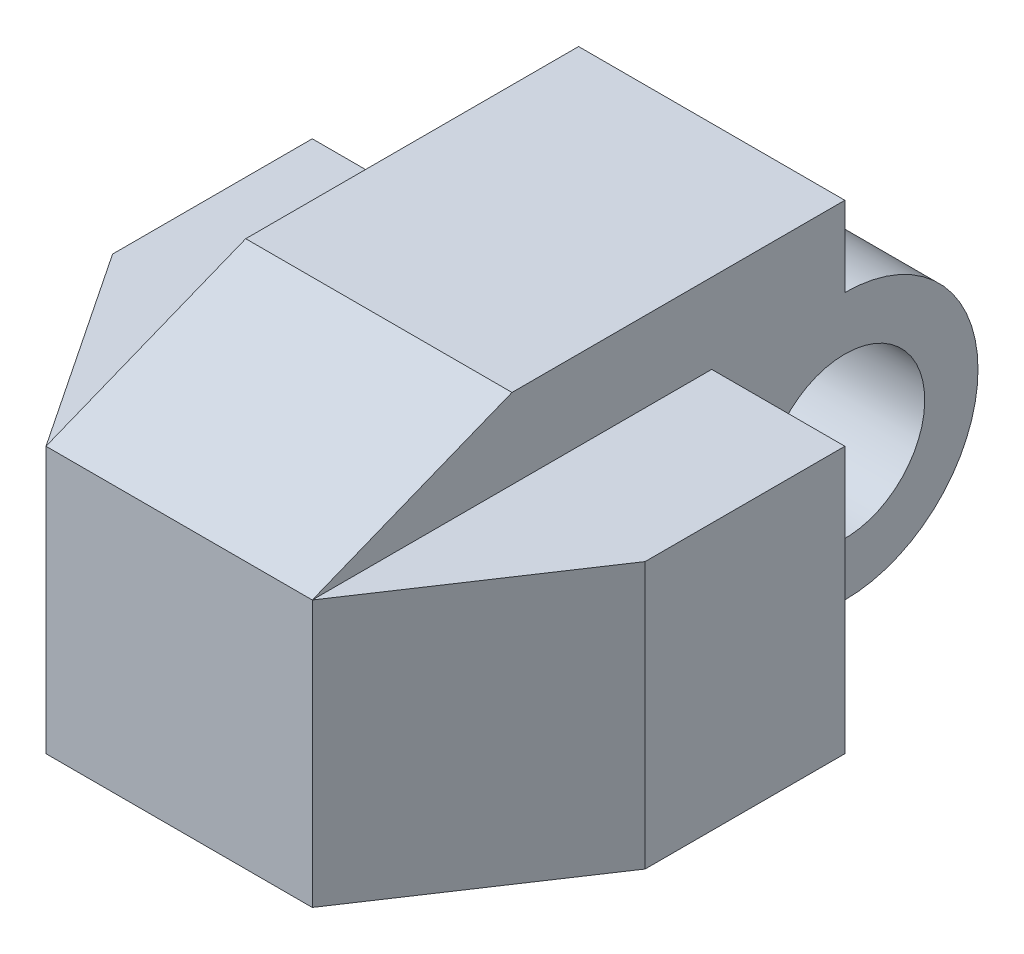
SolidWorks part; units mm, degrees
ref_plane "Front Plane" through (0, 0, 0) normal (0, 0, 1) x (1, 0, 0)
ref_plane "Top Plane" through (0, 0, 0) normal (0, 1, 0) x (1, 0, 0)
ref_plane "Right Plane" through (0, 0, 0) normal (1, 0, 0) x (0, 0, -1)
sketch "Sketch1" plane through (0, 0, 0) normal (0, 0, 1) x (1, 0, 0)
  line L2 (-3.6788, 4.8964) -> (6.3212, 4.8964)
  line L3 (-3.6788, 4.8964) -> (-3.6788, -5.1036)
  line L4 (-3.6788, -5.1036) -> (6.3212, -5.1036)
  line L5 (6.3212, 4.8964) -> (6.3212, -5.1036)
  dimension "D1" = 10
  dimension "D2" = 10
extrude "Boss-Extrude1" add sketch "Sketch1" along normal blind 10
sketch "Sketch2" plane through (6.3212, 0, 0) normal (1, 0, 0) x (0, 0, -1)
  circle A0 centre (-5, -0.1036) radius 3
extrude "Cut-Extrude1" cut sketch "Sketch2" against normal blind 10
fillet "Fillet2" radius 5 2 edges at (1.3212, -5.1036, 0) (1.3212, 4.8964, 0)
sketch "Sketch3" plane through (0, 0, 10) normal (0, 0, 1) x (1, 0, 0)
  line L0 (6.3212, 4.8964) -> (-3.6788, 4.8964) construction
  line L1 (-8.6788, 4.8964) -> (11.3212, 4.8964)
  line L2 (-8.6788, 4.8964) -> (-8.6788, -5.1036)
  line L3 (-8.6788, -5.1036) -> (11.3212, -5.1036)
  line L4 (11.3212, 4.8964) -> (11.3212, -5.1036)
  line L5 (-3.6788, 4.8964) -> (-3.6788, -5.1036) construction
  dimension "D1" = 0
  dimension "D2" = 10
  dimension "D3" = 20
  dimension "D4" = 5
extrude "Boss-Extrude3" add sketch "Sketch3" along normal blind 15
sketch "Sketch4" plane through (0, 4.8964, 0) normal (0, 1, 0) x (1, 0, 0)
  line L0 (-8.6788, -25) -> (-8.6788, -10) construction
  line L13 (6.3212, -25) -> (11.3212, -17.5)
  line L14 (11.3212, -25) -> (-8.6788, -25) construction
  line L17 (-3.6788, -25) -> (-8.6788, -17.5)
  line L18 (11.3212, -25) -> (11.3212, -17.5)
extrude "Cut-Extrude2" cut sketch "Sketch4" against normal blind 15
sketch "Sketch5" plane through (0, 4.8964, 0) normal (0, 1, 0) x (1, 0, 0)
  line L1 (-3.6788, -5) -> (6.3212, -5)
  line L2 (-3.6788, -5) -> (-3.6788, -25)
  line L3 (-3.6788, -25) -> (6.3212, -25)
  line L4 (6.3212, -5) -> (6.3212, -25)
extrude "Boss-Extrude4" add sketch "Sketch5" along normal blind 3
sketch "Sketch6" plane through (-3.6788, 0, 0) normal (-1, 0, 0) x (0, 0, 1)
  line L1 (5, 7.8964) -> (25, 7.8964) construction
  line L2 (17.5, 7.8964) -> (25, 4.8964)
  line L3 (25, 4.8964) -> (25, 7.8964)
  line L4 (25, 7.8964) -> (17.5, 7.8964)
extrude "Cut-Extrude3" cut sketch "Sketch6" against normal blind 10
